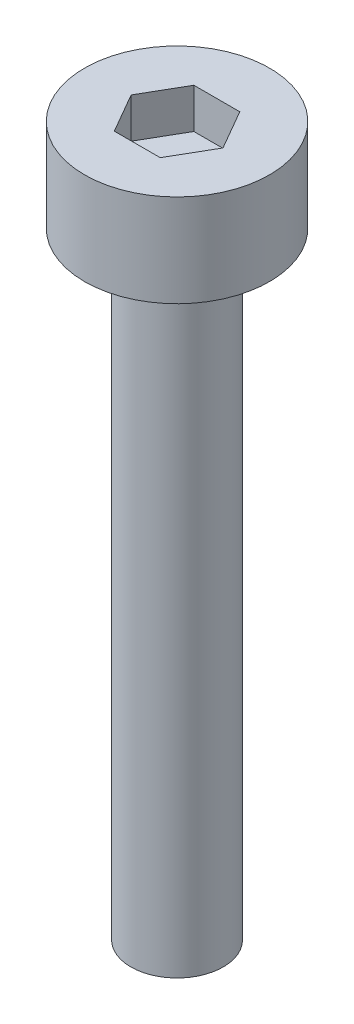
SolidWorks part; units mm, degrees
ref_plane "Front Plane" through (0, 0, 0) normal (0, 0, 1) x (1, 0, 0)
ref_plane "Top Plane" through (0, 0, 0) normal (0, 1, 0) x (1, 0, 0)
ref_plane "Right Plane" through (0, 0, 0) normal (1, 0, 0) x (0, 0, -1)
sketch "Sketch1" plane through (0, 0, 0) normal (0, 1, 0) x (1, 0, 0)
  circle A0 centre (0, 0) radius 1.5
  dimension "D1" = 3
extrude "ScrewShaft" add sketch "Sketch1" along normal blind 20
sketch "Sketch2" plane through (0, 20, 0) normal (0, 1, 0) x (1, 0, 0)
  circle A0 centre (0, 0) radius 3
  dimension "D1" = 6
extrude "Boss-Extrude2" add sketch "Sketch2" along normal blind 3
sketch "Sketch3" plane through (0, 23, 0) normal (0, 1, 0) x (1, 0, 0)
  line L0 (0, 0) -> (0, 1.29) construction
  line L1 (1.4896, 0) -> (0.7448, 1.29)
  line L2 (0.7448, 1.29) -> (-0.7448, 1.29)
  line L3 (-0.7448, 1.29) -> (-1.4896, 0)
  line L4 (-1.4896, 0) -> (-0.7448, -1.29)
  line L5 (-0.7448, -1.29) -> (0.7448, -1.29)
  line L6 (0.7448, -1.29) -> (1.4896, 0)
  circle A0 centre (0, 0) radius 1.29 construction
  dimension "D1" = 2.58
extrude "Cut-Extrude1" cut sketch "Sketch3" against normal blind 1.3
equation "\"X-ROD-SPACING\"=45"
equation "\"Y-ROD-SPACING\"=75"
equation "\"Z-ROD-SPACING\"=17.5"
equation "\"Y-BED-OFFSET\"=2"
equation "\"Y-BED-ROD-INSET\"=3.5"
equation "\"T-SLOT-NUT-FILLET-RADIUS\"=0.25"
equation "\"T-SLOT-SCREW-SHAFT-RADIUS\"=1.75"
equation "\"T-SLOT-SCREW-SHAFT-CUTOUT-LENGTH\"=10.5"
equation "\"T-SLOT-NUT-DEPTH\"=4.2"
equation "\"T-SLOT-NUT-WIDTH\"=3"
equation "\"T-SLOT-NUT-END-DISTANCE\"=8"
equation "\"ACRYLIC-THICKNESS\"=10"
equation "\"ACRYLIC-THICKNESS2\"=4.5"
equation "\"ACRYLIC-TAB-CUTOUT-SIZE\"=\"ACRYLIC-THICKNESS\"+\"ACRYLIC-TAB-TOLERANCE\"*2"
equation "\"ACRYLIC-TAB-WIDTH\"=\"ACRYLIC-THICKNESS\""
equation "\"ACRYLIC-M3-HOLE\"=3.2"
equation "\"SMOOTHROD-CAP-SCREW-DISTANCE\"=20"
equation "\"FRAME-WIDTH-INNER\"=370"
equation "\"NEMA17-HOLE-SPACING\"=31"
equation "\"NEMA17-CENTRAL-CUTOUT\"=22.5"
equation "\"Z-BRACKET-REACH\"=55"
equation "\"TOP-BRACKET-SPACING\"=40"
equation "\"SMOOTHROD-X-LENGTH\"=350"
equation "\"SMOOTHROD-Y-LENGTH\"=350"
equation "\"SMOOTHROD-Z-LENGTH\"=350"
equation "\"SMOOTHROD-TIGHTENING-HEADROOM\"=1"
equation "\"LEADSCREW-Z-LENGTH\"=300"
equation "\"SCREW-LENGTH-FRAME\"=\"ACRYLIC-THICKNESS\" + 10"
equation "\"SCREW-HEAD-RADIUS\"=6"
equation "\"PRINTED-X-SMOOTHROD-DIAMETER\"=8.2"
equation "\"PRINTED-X-SMOOTHROD-CUTOUT\"=10"
equation "\"PRINTED-X-BASE-HEIGHT\"=10"
equation "\"PRINTED-LM8UU-CUTOUT-SIZE\"=15.25"
equation "\"PRINTED-LM8UU-CUTOUT-LENGTH\"=24.5"
equation "\"PRINTED-X-IDLER-HEIGHT\"=16"
equation "\"PSU-MOUNTING-WIDTH\"=95"
equation "\"PSU-MOUNTING-HEIGHT\"=177"
equation "\"D1@ScrewShaft\"=\"SCREW-LENGTH-FRAME\""
equation "\"D1@Sketch2\"=\"SCREW-HEAD-RADIUS\""
